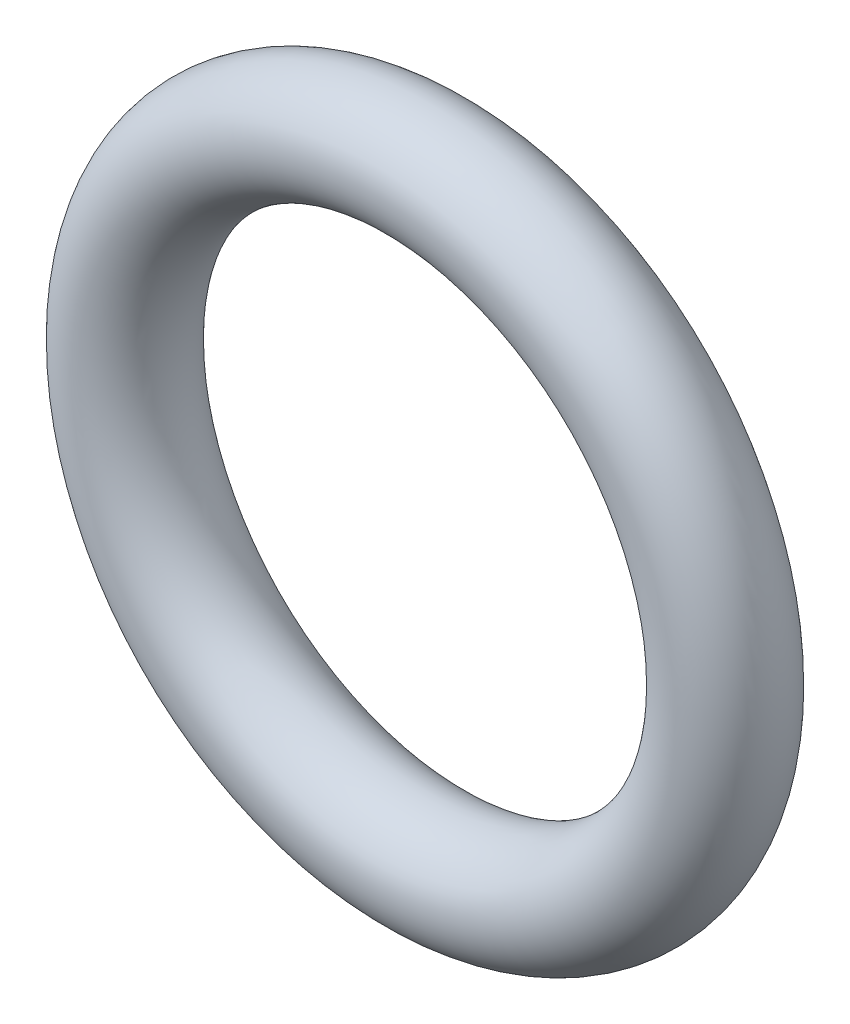
SolidWorks part; units mm, degrees
material "Резина"
ref_plane "Спереди" through (0, 0, 0) normal (0, 0, 1) x (1, 0, 0)
ref_plane "Сверху" through (0, 0, 0) normal (0, 1, 0) x (1, 0, 0)
ref_plane "Справа" through (0, 0, 0) normal (1, 0, 0) x (0, 0, -1)
sketch "Эскиз1" plane through (0, 0, 0) normal (0, 1, 0) x (1, 0, 0)
  line L0 (0, 0) -> (0, 5.3333) construction
  circle A0 centre (6.75, 0) radius 1.25
  point P2 (8, 0)
  dimension "D1" = 2.5
  dimension "D2" = 16
revolve "Повернуть1" add sketch "Эскиз1" angle 360 about L0
